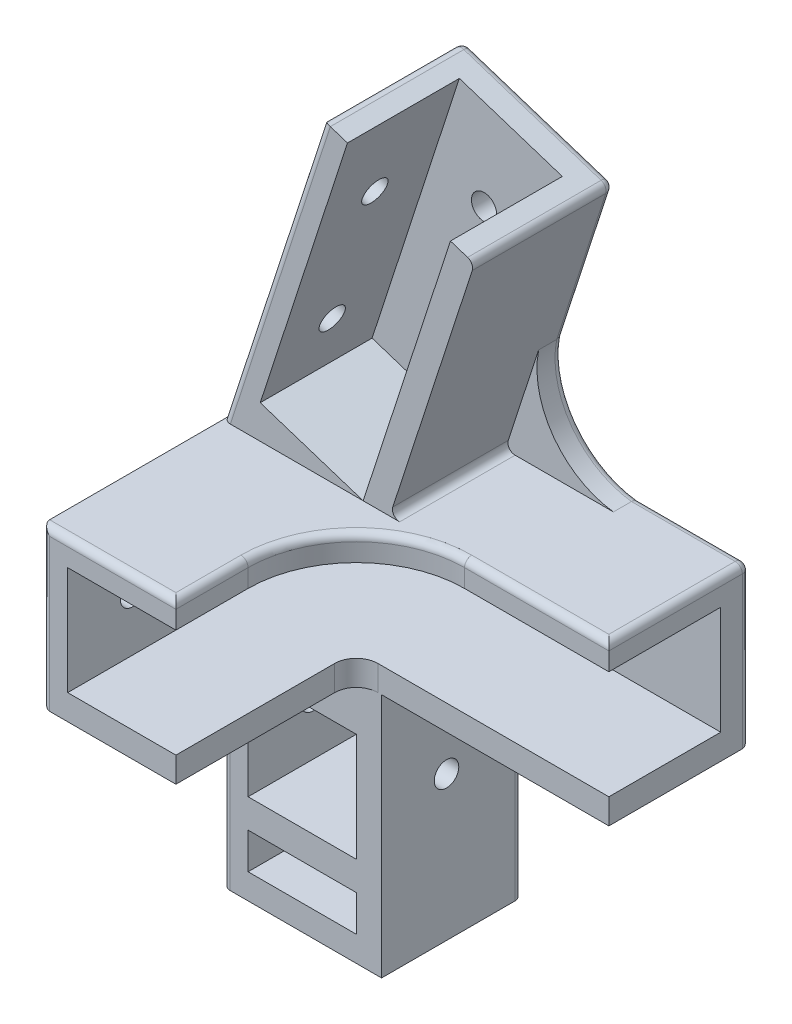
SolidWorks part; units mm, degrees
ref_plane "Front Plane" through (0, 0, 0) normal (0, 0, 1) x (1, 0, 0)
ref_plane "Top Plane" through (0, 0, 0) normal (0, 1, 0) x (1, 0, 0)
ref_plane "Right Plane" through (0, 0, 0) normal (1, 0, 0) x (0, 0, -1)
sketch "Sketch1" plane through (0, 0, 0) normal (0, 0, 1) x (1, 0, 0)
  line L1 (-5.6994, 32.9163) -> (16.3006, 32.9163)
  line L2 (-5.6994, 10.9163) -> (-5.6994, -23.0837)
  line L3 (-5.6994, -23.0837) -> (16.3006, -23.0837)
  line L4 (16.3006, 32.9163) -> (16.3006, -23.0837)
  line L5 (-5.6994, 10.9163) -> (-37.1994, 10.9163)
  line L7 (-5.6994, 32.9163) -> (-37.1994, 32.9163)
  line L8 (-37.1994, 10.9163) -> (-37.1994, 32.9163)
  dimension "D1" = 22
  dimension "D2" = 22
  dimension "D3" = 56
  dimension "D4" = 53.5
extrude "Boss-Extrude1" add sketch "Sketch1" along normal blind 19.5
sketch "Sketch3" plane through (0, 0, 19.5) normal (0, 0, 1) x (1, 0, 0)
  line L1 (16.3006, 32.9163) -> (-2.1994, 32.9163)
  line L2 (16.3006, 32.9163) -> (16.3006, 10.9163)
  line L3 (16.3006, 10.9163) -> (-2.1994, 10.9163)
  line L4 (-2.1994, 32.9163) -> (-2.1994, 10.9163)
  dimension "D1" = 18.5
extrude "Boss-Extrude2" add sketch "Sketch3" along normal blind 25
sketch "Sketch5" plane through (0, 0, 44.5) normal (0, 0, 1) x (1, 0, 0)
  line L0 (-37.1994, 32.9163) -> (-37.1994, 10.9163) construction
  line L1 (-37.1994, 29.4163) -> (12.8006, 29.4163)
  line L2 (-37.1994, 29.4163) -> (-37.1994, 14.4163)
  line L3 (-37.1994, 14.4163) -> (12.8006, 14.4163)
  line L4 (12.8006, 29.4163) -> (12.8006, 14.4163)
  line L5 (16.3006, 10.9163) -> (16.3006, 32.9163) construction
  line L6 (-2.1994, 4.4163) -> (12.8006, 4.4163)
  line L7 (-2.1994, 4.4163) -> (-2.1994, -10.5837)
  line L8 (-2.1994, -10.5837) -> (12.8006, -10.5837)
  line L9 (12.8006, 4.4163) -> (12.8006, -10.5837)
  line L12 (-2.1994, 32.9163) -> (-37.1994, 32.9163) construction
  line L13 (-2.1994, 10.9163) -> (16.3006, 10.9163) construction
  line L15 (16.3006, -23.0837) -> (16.3006, 10.9163) construction
  line L16 (-5.6994, -23.0837) -> (16.3006, -23.0837) construction
  line L17 (-2.1994, -14.5837) -> (12.8006, -14.5837)
  line L18 (-2.1994, -14.5837) -> (-2.1994, -19.5837)
  line L19 (-2.1994, -19.5837) -> (12.8006, -19.5837)
  line L20 (12.8006, -14.5837) -> (12.8006, -19.5837)
  dimension "D1" = 3.5
  dimension "D2" = 6.5
  dimension "D3" = 15
  dimension "D4" = 3.5
  dimension "D5" = 15
  dimension "D6" = 15
  dimension "D7" = 3.5
  dimension "D8" = 15
  dimension "D9" = 4
  dimension "D10" = 3.5
extrude "Cut-Extrude1" cut sketch "Sketch5" against normal offset from surface (40.5 mm away) 4 up to face at (-8.8661, 6.9163, 0)
sketch "Sketch7" plane through (16.3006, 0, 0) normal (1, 0, 0) x (0, 0, -1)
  line L0 (-34.5, 10.9163) -> (-19.5, 10.9163)
  line L1 (-44.5, 10.9163) -> (-19.5, 10.9163) construction
  line L2 (-19.5, 10.9163) -> (-19.5, -4.0837)
  line L3 (-19.5, -23.0837) -> (-19.5, 10.9163) construction
  arc A0 (-34.5, 10.9163) -> (-19.5, -4.0837) centre (-34.5, -4.0837) cw
  dimension "D1" = 15
extrude "Boss-Extrude4" add sketch "Sketch7" against normal blind 3.5
sketch "Sketch8" plane through (0, 0, 0) normal (0, 0, -1) x (-1, 0, 0)
  line L0 (5.6994, 10.9163) -> (20.6994, 10.9163)
  line L1 (37.1994, 10.9163) -> (5.6994, 10.9163) construction
  line L2 (5.6994, 10.9163) -> (5.6994, -4.0837)
  line L3 (5.6994, 10.9163) -> (5.6994, -23.0837) construction
  arc A0 (20.6994, 10.9163) -> (5.6994, -4.0837) centre (20.6994, -4.0837) ccw
  dimension "D1" = 15
extrude "Boss-Extrude5" add sketch "Sketch8" against normal blind 3.5
sketch "Sketch9" plane through (0, 32.9163, 0) normal (0, 1, 0) x (1, 0, 0)
  line L0 (-2.1994, -34.5) -> (-2.1994, -19.5)
  line L1 (-2.1994, -44.5) -> (-2.1994, -19.5) construction
  line L2 (-2.1994, -19.5) -> (-17.1994, -19.5)
  line L3 (-2.1994, -19.5) -> (-37.1994, -19.5) construction
  arc A0 (-2.1994, -34.5) -> (-17.1994, -19.5) centre (-17.1994, -34.5) ccw
  dimension "D1" = 15
extrude "Boss-Extrude6" add sketch "Sketch9" against normal blind 3.5
fillet "Fillet3" radius 3 1 edges
sketch "Sketch11" plane through (0, 0, 0) normal (0, 0, -1) x (-1, 0, 0)
  line L0 (1.1994, -23.0837) -> (1.1994, 10.9163) construction
  line L2 (5.6994, -23.0837) -> (-16.3006, -23.0837) construction
  line L5 (5.6994, -4.0837) -> (5.6994, -23.0837) construction
  text T0 "MR.3" font "Century Gothic" height 12
  dimension "D1" = 4.5
extrude "Cut-Extrude3" cut sketch "Sketch11" against normal blind 1
sketch "Sketch12" plane through (0, 0, 0) normal (0, 0, -1) x (-1, 0, 0)
  line L0 (37.1994, 21.9163) -> (-16.3006, 21.9163) construction
  line L1 (37.1994, 32.9163) -> (37.1994, 10.9163) construction
  line L2 (-16.3006, -23.0837) -> (-16.3006, 32.9163) construction
  line L3 (-12.8006, 14.4163) -> (-12.8006, 29.4163) construction
  circle A0 centre (-5.3006, 21.9163) radius 1.7
  circle A1 centre (10.9494, 21.9163) radius 1.7
  circle A2 centre (27.1994, 21.9163) radius 1.7
  dimension "D4" = 3.4
  dimension "D1" = 7.5
  dimension "D2" = 10
  dimension "D3" = 16.25
extrude "Cut-Extrude4" cut sketch "Sketch12" against normal blind 5
sketch "Sketch13" plane through (-5.6994, 0, 0) normal (-1, 0, 0) x (0, 0, 1)
  line L0 (4, 4.4163) -> (19.5, 4.4163) construction
  line L1 (19.5, 10.9163) -> (19.5, -23.0837) construction
  circle A0 centre (10.5, -3.0837) radius 1.7
  dimension "D2" = 9
  dimension "D3" = 3.4
  dimension "D1" = 7.5
extrude "Cut-Extrude5" cut sketch "Sketch13" against normal blind 45
sketch "Sketch14" plane through (16.3006, 0, 0) normal (1, 0, 0) x (0, 0, -1)
  line L0 (-10.5, -3.0837) -> (-10.5, 32.9163) construction
  line L1 (-44.5, 32.9163) -> (0, 32.9163) construction
  line L2 (-44.5, 21.9163) -> (-10.5, 21.9163) construction
  line L3 (-44.5, 10.9163) -> (-44.5, 32.9163) construction
  circle A0 centre (-10.5, 21.9163) radius 1.7
  circle A1 centre (-35.5, 21.9163) radius 1.7
  dimension "D1" = 3.4
  dimension "D2" = 9
extrude "Cut-Extrude6" cut sketch "Sketch14" against normal blind 45
sketch "Sketch15" plane through (0, -23.0837, 0) normal (0, -1, 0) x (1, 0, 0)
  line L0 (16.3006, 9.75) -> (-5.6994, 9.75) construction
  line L1 (16.3006, 19.5) -> (16.3006, 0) construction
  line L2 (-5.6994, 19.5) -> (-5.6994, 0) construction
  line L3 (5.3006, 19.5) -> (5.3006, 0) construction
  line L4 (-5.6994, 19.5) -> (16.3006, 19.5) construction
  line L5 (-5.6994, 0) -> (16.3006, 0) construction
  circle A0 centre (5.3006, 9.75) radius 1.7
  dimension "D1" = 3.4
extrude "Cut-Extrude7" cut sketch "Sketch15" against normal blind 4
mirror "Mirror2" about plane through (16.3006, 32.9163, 19.5) normal (-1, 0, 0) of "Cut-Extrude7", "Cut-Extrude6", "Cut-Extrude5", "Cut-Extrude4", "Fillet3", "Boss-Extrude6", "Boss-Extrude5", "Boss-Extrude4", "Cut-Extrude1", "Boss-Extrude2", "Boss-Extrude1"
sketch "Sketch16" plane through (0, 0, 0) normal (0, 0, -1) x (-1, 0, 0)
  line L0 (-69.8006, 32.9163) -> (37.1994, 32.9163) construction
  line L1 (-16.3006, 32.9163) -> (53.9943, 32.9163)
  line L2 (-16.3006, 32.9163) -> (-16.3006, -24.95)
  line L3 (-16.3006, -24.95) -> (53.9943, -24.95)
  line L4 (53.9943, 32.9163) -> (53.9943, -24.95)
extrude "Cut-Extrude8" cut sketch "Sketch16" against normal blind 72
sketch "Sketch20" plane through (0, 0, 0) normal (0, 0, -1) x (-1, 0, 0)
  line L0 (-22.3006, -23.0837) -> (-22.3006, 16.9163) construction
  line L1 (-16.3006, -23.0837) -> (-38.3006, -23.0837) construction
  line L2 (-16.3006, 32.9163) -> (-16.3006, -23.0837) construction
  text T0 "ALFR3D" font "Murder Of Mayday" height 10
  dimension "D1" = 6
  dimension "D2" = 40
extrude "Cut-Extrude9" [suppressed] cut sketch "Sketch20" against normal blind 1
sketch "Sketch21" plane through (0, 0, 0) normal (0, 0, -1) x (-1, 0, 0)
  line L0 (-16.3006, 32.9163) -> (-30.2522, 75.8548)
  line L1 (-30.2522, 75.8548) -> (-51.1754, 69.0564)
  line L2 (-51.1754, 69.0564) -> (-39.4328, 32.9163)
  line L3 (-69.8006, 32.9163) -> (-16.3006, 32.9163) construction
  line L4 (-39.4328, 32.9163) -> (-16.3006, 32.9163)
  dimension "D1" = 22
  dimension "D2" = 72
  dimension "D3" = 38
extrude "Boss-Extrude7" add sketch "Sketch21" against normal up to surface (19.5 mm away) up to face at (57.3006, 31.1663, 19.5)
sketch "Sketch22" plane through (0, 0, 19.5) normal (0, 0, 1) x (1, 0, 0)
  line L0 (33.5809, 74.7732) -> (21.4868, 37.5515)
  line L1 (51.1754, 69.0564) -> (30.2522, 75.8548) construction
  line L2 (21.4868, 37.5515) -> (35.7526, 32.9163)
  line L3 (35.7526, 32.9163) -> (47.8467, 70.138)
  line L4 (47.8467, 70.138) -> (33.5809, 74.7732)
  line L5 (30.2522, 75.8548) -> (16.3006, 32.9163) construction
  line L7 (16.3006, 32.9163) -> (39.4328, 32.9163) construction
  dimension "D1" = 15
  dimension "D2" = 3.5
extrude "Cut-Extrude10" cut sketch "Sketch22" against normal up to surface (15.5 mm away) up to face at (41.8506, 21.9163, 4)
sketch "Sketch23" plane through (0, 0, 0) normal (0, 0, -1) x (-1, 0, 0)
  line L0 (-54.4328, 32.9163) -> (-39.4328, 32.9163)
  line L1 (-69.8006, 32.9163) -> (-39.4328, 32.9163) construction
  line L2 (-39.4328, 32.9163) -> (-44.068, 47.1821)
  line L3 (-51.1754, 69.0564) -> (-39.4328, 32.9163) construction
  arc A0 (-54.4328, 32.9163) -> (-44.068, 47.1821) centre (-55.836, 44.8339) ccw
  dimension "D2" = 12
  dimension "D1" = 15
extrude "Boss-Extrude8" add sketch "Sketch23" against normal blind 3.5
fillet "Fillet4" radius 1 22 edges at (16.3006, 10.9163, 39.5) (16.3006, 6.5229, 23.8934) (61.5506, 10.9163, 0) (42.694, 6.5229, 0) (34.8006, 32.9163, 39.5) (46.1278, 37.7805, 0) (23.2764, 54.3855, 0) (16.3006, -13.5837, 19.5) (16.3006, 4.9163, 0) (38.3006, -13.5837, 0) (69.8006, 32.9163, 9.75) (69.8006, 21.9163, 0) (16.3006, 21.9163, 44.5) (39.194, 32.9163, 23.8934) (25.5506, 32.9163, 44.5) (30.2522, 75.8548, 9.75) (40.7138, 72.4556, 0) (51.1754, 69.0564, 9.75)
fillet "Fillet5" radius 1 1 edges
sketch "Sketch24" plane through (5.0702, -1.6474, 0) normal (-0.9511, 0.309, 0) x (0, 0, 1)
  line L0 (12, 36.3424) -> (12, 88.887) construction
  line L1 (18.5, 36.3424) -> (1, 36.3424) construction
  line L2 (19.5, 81.4906) -> (19.5, 36.6673) construction
  line L3 (1, 81.4906) -> (19.5, 81.4906) construction
  line L5 (4, 42.3534) -> (19.5, 42.3534) construction
  circle A0 centre (12, 69.4906) radius 1.75
  circle A1 centre (12, 50.3534) radius 1.75
  dimension "D2" = 3.5
  dimension "D3" = 12
  dimension "D4" = 8
  dimension "D1" = 7.5
extrude "Cut-Extrude11" cut sketch "Sketch24" against normal blind 10
sketch "Sketch25" plane through (0, 0, 0) normal (0, 0, -1) x (-1, 0, 0)
  line L0 (-40.7138, 72.4556) -> (-28.6197, 35.2339) construction
  line L1 (-50.2243, 69.3654) -> (-31.2032, 75.5458) construction
  line L2 (-21.4868, 37.5515) -> (-35.7526, 32.9163) construction
  line L3 (-21.171, 47.9059) -> (-24.4997, 46.8243) construction
  circle A0 centre (-37.0056, 61.0429) radius 1.75
  circle A1 centre (-31.0146, 42.6046) radius 1.75
  dimension "D1" = 3.5
  dimension "D2" = 12
  dimension "D3" = 2
extrude "Cut-Extrude12" cut sketch "Sketch25" against normal blind 10
